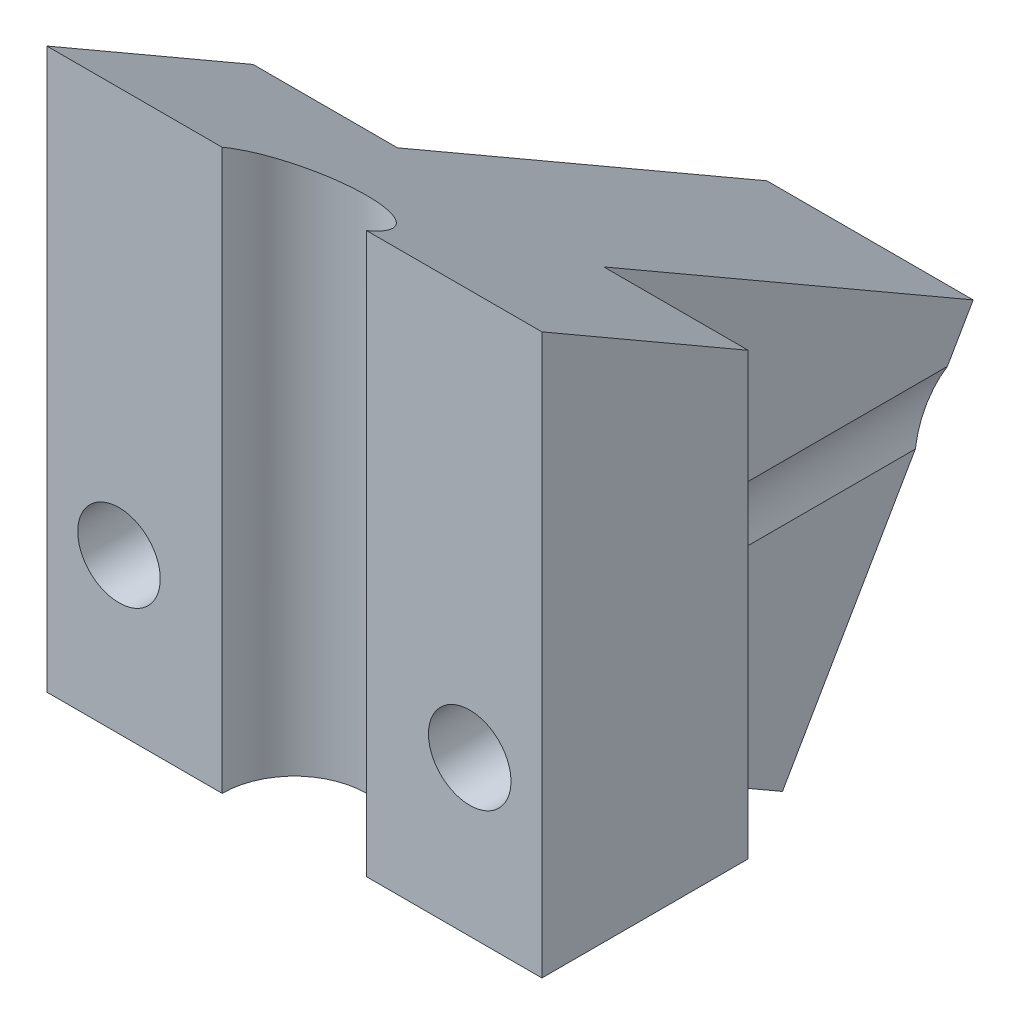
SolidWorks part; units mm, degrees
ref_plane "Спереди" through (0, 0, 0) normal (0, 0, 1) x (1, 0, 0)
ref_plane "Сверху" through (0, 0, 0) normal (0, 1, 0) x (1, 0, 0)
ref_plane "Справа" through (0, 0, 0) normal (1, 0, 0) x (0, 0, -1)
sketch "Эскиз1" plane through (0, 0, 0) normal (0, 1, 0) x (1, 0, 0)
  line L1 (-24, -10) -> (24, -10)
  line L2 (-24, -10) -> (-24, 10)
  line L3 (-24, 10) -> (24, 10)
  line L4 (24, -10) -> (24, 10)
  line L5 (-24, -10) -> (24, 10) construction
  line L6 (-24, 10) -> (24, -10) construction
  point P0 (0, 0)
  dimension "D1" = 48
  dimension "D2" = 20
extrude "Бобышка-Вытянуть1" add sketch "Эскиз1" along normal blind 30
sketch "Эскиз2" plane through (0, 0, 10) normal (0, 0, 1) x (1, 0, 0)
  line L0 (-7, 30) -> (-7, 0)
  line L1 (-24, 30) -> (24, 30) construction
  line L2 (-24, 0) -> (24, 0) construction
  line L3 (-7, 0) -> (7, 0)
  line L4 (7, 0) -> (7, 30)
  line L5 (7, 30) -> (-7, 30)
  dimension "D1" = 17
  dimension "D2" = 14
extrude "Вырез-Вытянуть1" cut sketch "Эскиз2" against normal blind 7
sketch "Эскиз7" plane through (24, 0, 0) normal (1, 0, 0) x (0, 0, -1)
  line L0 (10, 0) -> (27.3205, -10) construction
  line L3 (-10, 0) -> (10, 0)
  line L4 (10, 0) -> (27.3205, -10)
  line L5 (10, 30) -> (32, 30)
  line L6 (32, 30) -> (45.8109, 22.0263)
  line L7 (27.3205, -10) -> (45.8109, 22.0263)
  line L8 (10, 0) -> (10, 30)
  line M4 (10, 0) -> (10, 30)
  dimension "D1" = 150
  dimension "D2" = 20
  dimension "D3" = 22
extrude "Бобышка-Вытянуть2" add sketch "Эскиз7" against normal blind 48 contours L4 L7 L6 L5 M4 region at (24, 13.2668, -24.7301)
sketch "Эскиз8" plane through (24, 0, 0) normal (1, 0, 0) x (0, 0, -1)
  line L0 (10, 0) -> (10, 30)
  line L1 (-10, 30) -> (32, 30) construction
  line L2 (10, 30) -> (32, 30)
  line L3 (32, 30) -> (45.8109, 22.0263)
  line L4 (45.8109, 22.0263) -> (27.3205, -10)
  line L5 (27.3205, -10) -> (10, 0)
extrude "Вырез-Вытянуть2" cut sketch "Эскиз8" against normal blind 14
sketch "Эскиз9" plane through (-24, 0, 0) normal (-1, 0, 0) x (0, 0, 1)
  line L0 (-10, 0) -> (-10, 30)
  line L1 (-32, 30) -> (10, 30) construction
  line L2 (-10, 30) -> (-32, 30)
  line L3 (-32, 30) -> (-45.8109, 22.0263)
  line L4 (-45.8109, 22.0263) -> (-27.3205, -10)
  line L5 (-27.3205, -10) -> (-10, 0)
extrude "Вырез-Вытянуть3" cut sketch "Эскиз9" against normal blind 14
sketch "Эскиз11" plane through (-10, 0, 0) normal (-1, 0, 0) x (0, 0, 1)
  line L0 (-36.449, 27.4314) -> (-16.9282, -4) construction
  line L1 (-27.3205, -10) -> (-10, 0) construction
  line L3 (-17.0853, 5.4822) -> (-27.2853, 23.1491)
  line L5 (-32, 30) -> (-45.8109, 22.0263) construction
  line L6 (-17.0853, 5.4822) -> (-26.0919, 0.2822)
  line L7 (-27.2853, 23.1491) -> (-36.2919, 17.9491)
  line L8 (-26.0919, 0.2822) -> (-36.2919, 17.9491)
  line L9 (-17.0853, 5.4822) -> (-36.2919, 17.9491) construction
  line L10 (-27.2853, 23.1491) -> (-26.0919, 0.2822) construction
  point P7 (-26.6886, 11.7157)
  point P8 (-26.6886, 11.7157)
  dimension "D1" = 20.4
  dimension "D2" = 10.4
  dimension "D3" = 12
extrude "Вырез-Вытянуть4" cut sketch "Эскиз11" against normal through all
sketch "Эскиз13" plane through (0, 0, -10) normal (0, 0, -1) x (-1, 0, 0)
  line L0 (24, 15) -> (10, 15) construction
  line L1 (24, 0) -> (24, 30) construction
  line L2 (10, 0) -> (10, 30) construction
  circle A0 centre (17, 15) radius 4
extrude "Вырез-Вытянуть5" cut sketch "Эскиз13" against normal through all
sketch "Эскиз14" plane through (0, 0, -10) normal (0, 0, -1) x (-1, 0, 0)
  line L0 (-24, 15) -> (-10, 15) construction
  line L1 (-24, 30) -> (-24, 0) construction
  line L2 (-10, 30) -> (-10, 0) construction
  circle A0 centre (-17, 15) radius 4
extrude "Вырез-Вытянуть6" cut sketch "Эскиз14" against normal through all
fillet "Скругление1" radius 7 2 edges at (-7, 15, 3) (7, 15, 3)
sketch "Эскиз16" plane through (10, 0, 0) normal (1, 0, 0) x (0, 0, -1)
  line L0 (27.2853, 23.1491) -> (17.0853, 5.4822)
  line L1 (17.0853, 5.4822) -> (26.0919, 0.2822)
  line L2 (26.0919, 0.2822) -> (36.2919, 17.9491)
  line L3 (36.2919, 17.9491) -> (27.2853, 23.1491)
extrude "Бобышка-Вытянуть3" add sketch "Эскиз16" against normal blind 3
sketch "Эскиз18" plane through (0, -14.3301, -24.8205) normal (0, -0.5, -0.866) x (-1, 0, 0)
  line L0 (-10, 23.4904) -> (10, 23.4904) construction
  line L1 (-10, 5) -> (-10, 41.9808) construction
  line L2 (10, 41.9808) -> (10, 5) construction
  text T0 "R" font "Arial" height 8
extrude "Бобышка-Вытянуть5" add sketch "Эскиз18" along normal blind 1
sketch "Эскиз20" plane through (0, 0, -10) normal (0, 0, -1) x (-1, 0, 0)
  circle A0 centre (-17, 15) radius 7.5
  circle A1 centre (17, 15) radius 7.5
  dimension "D1" = 15
extrude "Вырез-Вытянуть8" cut sketch "Эскиз20" along normal through all
sketch "Sketch3" plane through (0, 30, 0) normal (0, 1, 0) x (1, 0, 0)
  line L0 (7, -10) -> (24, -10)
  line L1 (24, -10) -> (24, 10)
  line L2 (24, 10) -> (10, 10)
  line L3 (10, 10) -> (10, 32)
  line L4 (10, 32) -> (-10, 32)
  line L5 (-10, 32) -> (-10, 10)
  line L6 (-10, 10) -> (-24, 10)
  line L7 (-24, 10) -> (-24, -10)
  line L8 (-24, -10) -> (-7, -10)
  arc A0 (-7, -10) -> (7, -10) centre (0, -10) cw
extrude "Boss-Extrude1" add sketch "Sketch3" along normal blind 25
sketch "Sketch4" plane through (-10, 0, 0) normal (-1, 0, 0) x (0, 0, 1)
  line L0 (-45.8109, 22.0263) -> (35.6307, 69.0466)
  line L1 (-32, 30) -> (-45.8109, 22.0263) construction
extrude "Cut-Extrude1" cut sketch "Sketch4" against normal through all both and the other way through all
